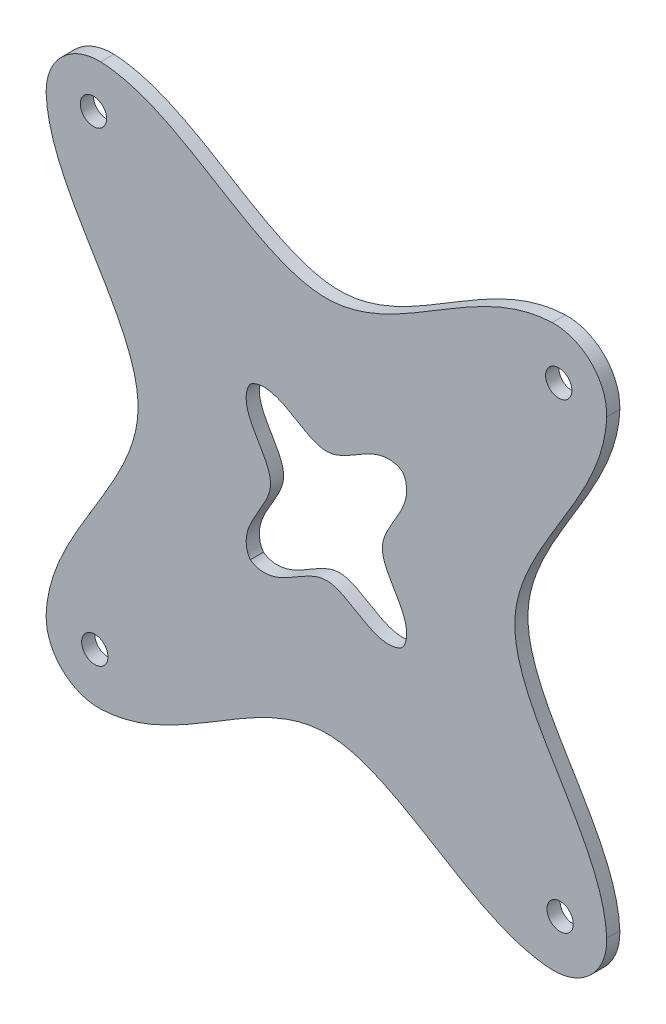
SolidWorks part; units mm, degrees
ref_plane "Front Plane" through (0, 0, 0) normal (0, 0, 1) x (1, 0, 0)
ref_plane "Top Plane" through (0, 0, 0) normal (0, 1, 0) x (1, 0, 0)
ref_plane "Right Plane" through (0, 0, 0) normal (1, 0, 0) x (0, 0, -1)
sketch "Sketch1" plane through (0, 0, 0) normal (0, 0, 1) x (1, 0, 0)
  line L1 (24.2824, -26.8224) -> (-24.2824, -26.8224) construction
  line L2 (26.8224, -24.2824) -> (26.8224, 24.2824) construction
  line L3 (24.2824, 26.8224) -> (-24.2824, 26.8224) construction
  line L4 (-26.8224, -24.2824) -> (-26.8224, 24.2824) construction
  line L5 (26.8224, -26.8224) -> (-26.8224, 26.8224) construction
  line L6 (26.8224, 26.8224) -> (-26.8224, -26.8224) construction
  line L7 (18.1737, 18.1737) -> (-18.1737, 18.1737) construction
  line L8 (18.1737, 18.1737) -> (18.1737, -18.1737) construction
  line L9 (18.1737, -18.1737) -> (-18.1737, -18.1737) construction
  line L10 (-18.1737, 18.1737) -> (-18.1737, -18.1737) construction
  line L11 (18.1737, 18.1737) -> (-18.1737, -18.1737) construction
  line L12 (18.1737, -18.1737) -> (-18.1737, 18.1737) construction
  spline S0 degree 3 poles (-26.0785, -26.0785) (-25.595, -26.4669) (-16.2014, -29.5054) (0, -7.6367) (16.2014, -29.5054) (25.595, -26.4669) (26.0785, -26.0785) knots 0.032767 0.032767 0.032767 0.032767 0.065534 0.5 0.934466 0.967233 0.967233 0.967233 0.967233
  spline S1 degree 3 poles (-26.0785, 26.0785) (-25.595, 26.4669) (-16.2014, 29.5054) (0, 7.6367) (16.2014, 29.5054) (25.595, 26.4669) (26.0785, 26.0785) knots 0.032767 0.032767 0.032767 0.032767 0.065534 0.5 0.934466 0.967233 0.967233 0.967233 0.967233
  spline S2 degree 3 poles (-26.0785, -26.0785) (-26.4669, -25.595) (-29.5054, -16.2014) (-7.6367, 0) (-29.5054, 16.2014) (-26.4669, 25.595) (-26.0785, 26.0785) knots 0.032767 0.032767 0.032767 0.032767 0.065534 0.5 0.934466 0.967233 0.967233 0.967233 0.967233
  spline S3 degree 3 poles (26.0785, -26.0785) (26.4669, -25.595) (29.5054, -16.2014) (7.6367, 0) (29.5054, 16.2014) (26.4669, 25.595) (26.0785, 26.0785) knots 0.032767 0.032767 0.032767 0.032767 0.065534 0.5 0.934466 0.967233 0.967233 0.967233 0.967233
  point P0 (0, 0)
  point P6 (0, 0)
  dimension "D1" = 53.6448
  dimension "D2" = 53.6448
extrude "Boss-Extrude1" add sketch "Sketch1" along normal blind 1.27
fillet "Fillet1" radius 5.08 3 edges at (26.0785, 26.0785, 0.635)
fillet "Fillet2" radius 5.08 3 edges at (-26.0785, -26.0785, 0.635)
fillet "Fillet3" radius 5.08 3 edges at (-26.0785, 26.0785, 0.635)
fillet "Fillet4" radius 5.08 3 edges at (26.0785, -26.0785, 0.635)
sketch "Sketch3" plane through (0, 0, 1.27) normal (0, 0, 1) x (1, 0, 0)
  line L1 (6.4389, 7.7089) -> (-6.4389, 7.7089) construction
  line L2 (7.7089, 6.4389) -> (7.7089, -6.4389) construction
  line L3 (6.4389, -7.7089) -> (-6.4389, -7.7089) construction
  line L4 (-7.7089, 6.4389) -> (-7.7089, -6.4389) construction
  line L5 (7.7089, 7.7089) -> (-7.7089, -7.7089) construction
  line L6 (7.7089, -7.7089) -> (-7.7089, 7.7089) construction
  line L7 (5.3975, 5.3975) -> (-5.3975, 5.3975) construction
  line L8 (5.3975, 5.3975) -> (5.3975, -5.3975) construction
  line L9 (5.3975, -5.3975) -> (-5.3975, -5.3975) construction
  line L10 (-5.3975, 5.3975) -> (-5.3975, -5.3975) construction
  line L11 (5.3975, 5.3975) -> (-5.3975, -5.3975) construction
  line L12 (5.3975, -5.3975) -> (-5.3975, 5.3975) construction
  circle A0 centre (-22.4839, 22.5633) radius 1.27 construction
  circle A1 centre (-22.4839, 22.5633) radius 1.27
  circle A2 centre (-22.3513, -22.3378) radius 1.27 construction
  circle A3 centre (-22.3513, -22.3378) radius 1.27
  circle A4 centre (22.5498, -22.2051) radius 1.27 construction
  circle A5 centre (22.5498, -22.2051) radius 1.27
  circle A6 centre (22.4183, 22.306) radius 1.27 construction
  circle A7 centre (22.4183, 22.306) radius 1.27
  spline S0 degree 3 poles (-7.3369, -7.3369) (-7.0946, -7.54) (-4.4417, -8.4675) (0, -2.7094) (4.4417, -8.4675) (7.0946, -7.54) (7.3369, -7.3369) knots 0.055321 0.055321 0.055321 0.055321 0.110642 0.5 0.889358 0.944679 0.944679 0.944679 0.944679
  spline S1 degree 3 poles (-7.3369, 7.3369) (-7.0946, 7.54) (-4.4417, 8.4675) (0, 2.7094) (4.4417, 8.4675) (7.0946, 7.54) (7.3369, 7.3369) knots 0.055321 0.055321 0.055321 0.055321 0.110642 0.5 0.889358 0.944679 0.944679 0.944679 0.944679
  spline S2 degree 3 poles (-7.3369, 7.3369) (-7.54, 7.0946) (-8.4675, 4.4417) (-2.7094, 0) (-8.4675, -4.4417) (-7.54, -7.0946) (-7.3369, -7.3369) knots 0.055321 0.055321 0.055321 0.055321 0.110642 0.5 0.889358 0.944679 0.944679 0.944679 0.944679
  spline S3 degree 3 poles (7.3369, 7.3369) (7.54, 7.0946) (8.4675, 4.4417) (2.7094, 0) (8.4675, -4.4417) (7.54, -7.0946) (7.3369, -7.3369) knots 0.055321 0.055321 0.055321 0.055321 0.110642 0.5 0.889358 0.944679 0.944679 0.944679 0.944679
  point P0 (0, 0)
  point P6 (0, 0)
  dimension "D1" = 15.4178
  dimension "D2" = 15.4178
extrude "Cut-Extrude1" cut sketch "Sketch3" against normal through all
